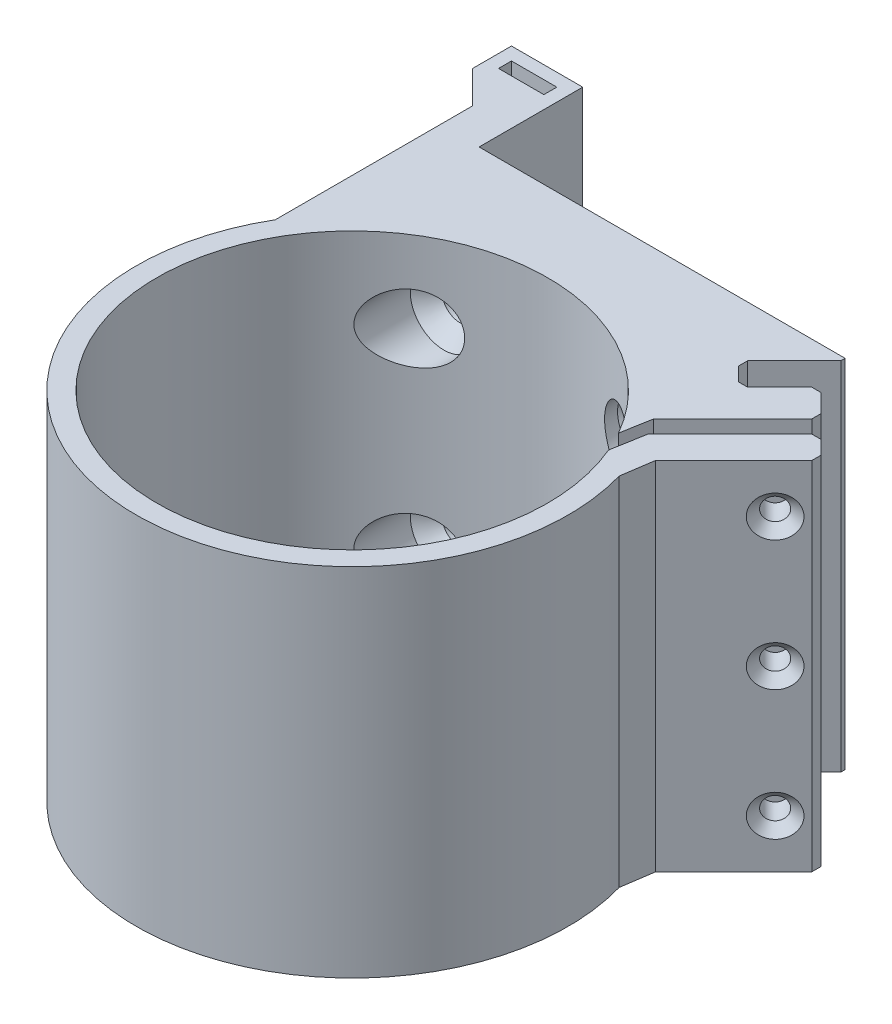
SolidWorks part; units mm, degrees
ref_plane "Front Plane" through (0, 0, 0) normal (0, 0, 1) x (1, 0, 0)
ref_plane "Top Plane" through (0, 0, 0) normal (0, 1, 0) x (1, 0, 0)
ref_plane "Right Plane" through (0, 0, 0) normal (1, 0, 0) x (0, 0, -1)
sketch "Sketch1" plane through (0, 0, 0) normal (0, 1, 0) x (1, 0, 0)
  line L0 (-28.75, 16.8768) -> (-28.75, 47.3375)
  line L5 (-33.75, 58.3375) -> (-22.75, 58.3375)
  line L6 (-22.75, 58.3375) -> (-22.75, 36.3375)
  line L7 (-22.75, 36.3375) -> (22.75, 36.3375)
  line L8 (22.75, 36.3375) -> (22.75, 42.3375)
  line L9 (22.75, 42.3375) -> (33.75, 42.3375)
  line L11 (27.0756, 19.4499) -> (26.2619, 14.8353)
  line L12 (28.6751, 17.0037) -> (27.7579, 11.8016)
  line L14 (27.0756, 19.4499) -> (39.9926, 32.3669)
  line L15 (28.6751, 17.0037) -> (42.0155, 30.3441)
  line L16 (42.0155, 30.3441) -> (45.5511, 26.8085)
  line L17 (45.5511, 26.8085) -> (31.0017, 12.2591)
  line L19 (35.75, 36.6096) -> (29.386, 30.2456)
  line L20 (29.386, 30.2456) -> (25.8505, 33.7812)
  line L21 (25.8505, 33.7812) -> (33.75, 41.6806)
  line L24 (35.75, 36.6096) -> (39.9926, 32.3669)
  line L25 (33.75, 41.6806) -> (33.75, 42.3375)
  line L26 (-33.75, 58.3375) -> (-33.75, 52.3375)
  line L27 (-33.75, 52.3375) -> (-28.75, 47.3375)
  line L35 (-31.75, 54.3375) -> (-24.75, 54.3375)
  line L36 (-31.75, 54.3375) -> (-31.75, 56.3375)
  line L37 (-31.75, 56.3375) -> (-24.75, 56.3375)
  line L38 (-24.75, 54.3375) -> (-24.75, 56.3375)
  line L39 (-31.75, 54.3375) -> (-24.75, 56.3375) construction
  line L40 (-31.75, 56.3375) -> (-24.75, 54.3375) construction
  arc A0 (-28.75, 16.8768) -> (31.0017, 12.2591) centre (0, 0) ccw
  arc A1 (26.2619, 14.8353) -> (27.7579, 11.8016) centre (0, 0) ccw
  arc A3 (31.0017, 12.2591) -> (-28.75, 16.8768) centre (0, 0) ccw construction
  circle A4 centre (0, 0) radius 32.1625 construction
  point P5 (0, 0)
  point P9 (0, 36.3375)
  point P12 (-28.25, 55.3375)
  point P13 (0, 33.3375)
  point P28 (-33.75, 54.9782)
  point P35 (0, 0)
  point P36 (0, 0)
  point P37 (-28.25, 58.3375)
  point P39 (-35.2226, 67.903)
  point P40 (-29.5936, 59.3926)
  point P41 (-30.0979, 70.4866)
  dimension "D2" = 3.175
  dimension "D4" = 30.1625
  dimension "D22" = 64.325
  dimension "D3" = 45.5
  dimension "D5" = 2
  dimension "D6" = 3
  dimension "D7" = 6
  dimension "D8" = 10
  dimension "D9" = 9
  dimension "D10" = 145
  dimension "D11" = 22
  dimension "D12" = 5
  dimension "D13" = 6
  dimension "D14" = 5
  dimension "D15" = 2
  dimension "D16" = 4
  dimension "D17" = 2
  dimension "D18" = 2
  dimension "D19" = 7
  dimension "D20" = 2
  dimension "D21" = 135
  dimension "D23" = 6
  dimension "D24" = 2
extrude "Boss-Extrude1" add sketch "Sketch1" along normal mid plane 55 contours A1 L11 L14 L19 L20 L21 L9 L8 L7 L6 L5 L0 A0 L17 L16 L15 L12 region at (-27.5379, 0, -32.1072)
hole_wizard "CSK for M3 Flat Head Machine Screw1" positions "Sketch2" profile "Sketch3" countersink size "M3" standard "ANSI Metric"
sketch "Sketch2" plane through (9.3713, 0, 9.3713) normal (0.7071, 0, 0.7071) x (0.7071, 0, -0.7071)
  line L2 (51.1659, 27.5) -> (51.1659, -27.5) construction
  point P0 (46.1659, 20)
  point P2 (46.1659, 0)
  point P4 (46.1659, -20)
  dimension "D1" = 20
  dimension "D2" = 20
  dimension "D3" = 5
sketch "Sketch3" plane through (42.0155, 20, -23.273) normal (0, 1, 0) x (0.7071, 0, -0.7071)
  line L0 (0, 0) -> (0, 21.0113)
  line L1 (0, 21.0113) -> (1.7, 19.9898)
  line L2 (1.7, 19.9898) -> (1.7, 1.45)
  line L3 (1.7, 1.45) -> (3.15, 0)
  line L5 (3.15, 0) -> (0, 0)
  line L6 (-1.7, 1.45) -> (-3.15, 0) construction
  line L10 (0, 21.0113) -> (-1.7, 19.9898) construction
  line L11 (0, -6.35) -> (0, 107.95) construction
  dimension "Hole Dia." = 3.4
  dimension "Hole Depth" = 19.9898
  dimension "Near C'Sink Dia." = 6.3
  dimension "Near C'Sink Angle" = 90
  dimension "Drill Angle" = 118
sketch "Sketch4" plane through (0, 27.5, 0) normal (0, -1, 0) x (1, 0, 0)
  line L1 (-22.75, -36.3375) -> (22.75, -36.3375)
  line L2 (-22.75, -36.3375) -> (-22.75, -42.3375)
  line L3 (-22.75, -42.3375) -> (22.75, -42.3375)
  line L4 (22.75, -36.3375) -> (22.75, -42.3375)
extrude "Boss-Extrude2" add sketch "Sketch4" along normal blind 4.5
ref_plane "Plane1" through (0, 0, -30.1625) normal (0, 0, 1) x (1, 0, 0)
sketch "Sketch6" plane through (0, 0, -30.1625) normal (0, 0, 1) x (1, 0, 0)
  line L1 (16, -15) -> (-16, -15) construction
  line L2 (16, -15) -> (16, 15) construction
  line L3 (16, 15) -> (-16, 15) construction
  line L4 (-16, -15) -> (-16, 15) construction
  line L5 (16, -15) -> (-16, 15) construction
  line L6 (16, 15) -> (-16, -15) construction
  point P0 (0, 0)
  dimension "D1" = 32
  dimension "D2" = 30
hole_wizard "CSK for M5 Flat Head Machine Screw1" positions "Sketch10" profile "Sketch12" countersink size "M5" standard "ANSI Metric" end condition through all
sketch "Sketch10" plane through (0, 0, -30.1625) normal (0, 0, 1) x (1, 0, 0)
  point P0 (-16, 15)
  point P3 (16, 15)
  point P6 (16, -15)
  point P9 (-16, -15)
sketch "Sketch12" plane through (-16, 15, -30.1625) normal (1, 0, 0) x (0, -1, 0)
  line L0 (0, 0) -> (0, 28.175)
  line L1 (0, 28.175) -> (2.75, 28.175)
  line L2 (2.75, 28.175) -> (2.75, 2.45)
  line L3 (2.75, 2.45) -> (5.2, 0)
  line L5 (5.2, 0) -> (0, 0)
  line L6 (-2.75, 2.45) -> (-5.2, 0) construction
  line L11 (0, -6.35) -> (0, 107.95) construction
  dimension "Thru Hole Dia." = 5.5
  dimension "Thru Hole Depth" = 28.175
  dimension "Near C'Sink Dia." = 10.4
  dimension "Near C'Sink Angle" = 90
sketch "Sketch13" plane through (0, 0, -30.1625) normal (0, 0, 1) x (1, 0, 0)
  circle A0 centre (-16, -15) radius 5.2 construction
  circle A1 centre (16, -15) radius 5.2 construction
  circle A2 centre (16, 15) radius 5.2 construction
  circle A3 centre (-16, 15) radius 5.2 construction
  circle A4 centre (-16, -15) radius 5.2
  circle A5 centre (16, -15) radius 5.2
  circle A6 centre (16, 15) radius 5.2
  circle A7 centre (-16, 15) radius 5.2
extrude "Cut-Extrude1" cut sketch "Sketch13" along normal up to next
chamfer "Chamfer1" distance 1 angle 45 6 edges at (45.5511, 0, -26.8085) (42.0155, 0, -30.3441) (29.386, 0, -30.2456) (25.8505, 0, -33.7812) (39.9926, 0, -32.3669) (35.75, 0, -36.6096)
chamfer "Chamfer2" distance 3 angle 30 1 edges at (31.0017, 0, -12.2591) first distance on face at (-0.7214, 0, 9.3352)
